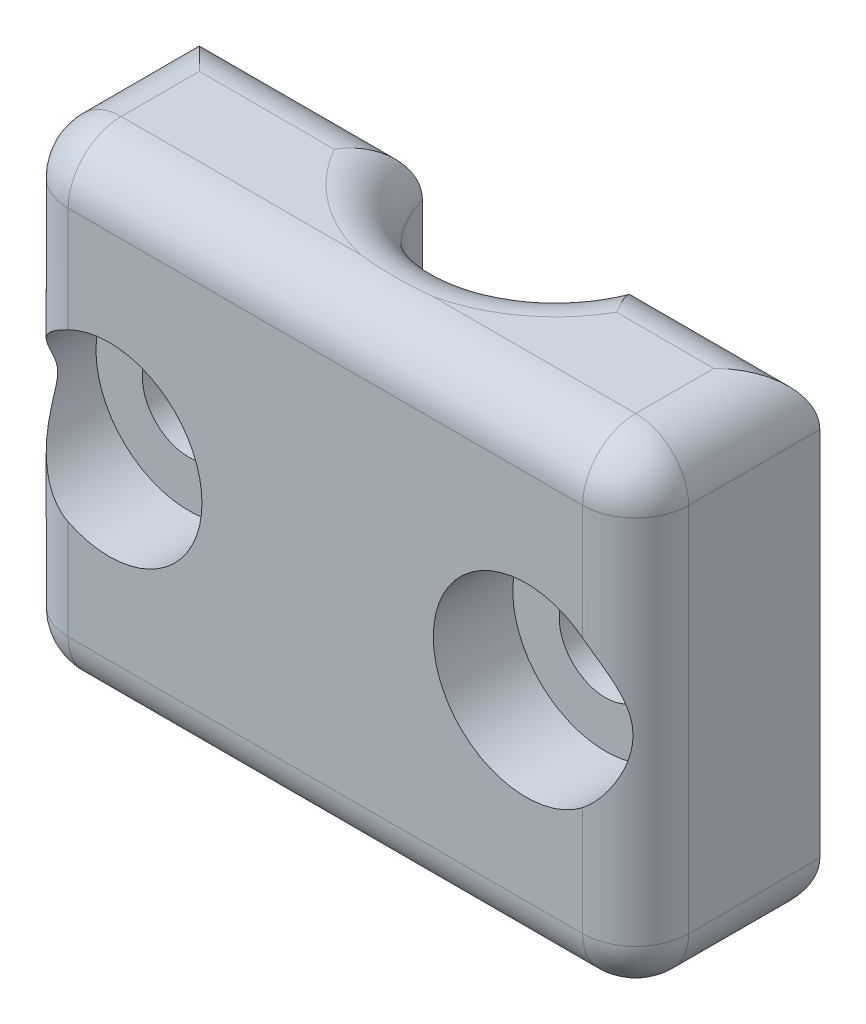
SolidWorks part; units mm, degrees
ref_plane "Front Plane" through (0, 0, 0) normal (0, 0, 1) x (1, 0, 0)
ref_plane "Top Plane" through (0, 0, 0) normal (0, 1, 0) x (1, 0, 0)
ref_plane "Right Plane" through (0, 0, 0) normal (1, 0, 0) x (0, 0, -1)
sketch "Sketch2" plane through (0, -22.2919, 0) normal (0, -1, 0) x (1, 0, 0)
  line L0 (9.0046, 3.0317) -> (0.5858, 3.0317)
  line L1 (24, 3.0317) -> (16.9954, 3.0317)
  line L2 (24, 3.0317) -> (24, 7.9815)
  line L3 (22, 9.9815) -> (2.5858, 9.9815)
  line L4 (0.5858, 3.0317) -> (0.5858, 7.9815)
  arc A1 (16.9954, 3.0317) -> (9.0046, 3.0317) centre (13, 2.0059) ccw
  arc A3 (2.5858, 9.9815) -> (0.5858, 7.9815) centre (2.5858, 7.9815) ccw
  arc A4 (24, 7.9815) -> (22, 9.9815) centre (22, 7.9815) ccw
  point P14 (0.5858, 9.9815)
  dimension "D1" = 2
extrude "Boss-Extrude1" add sketch "Sketch2" against normal blind 18
sketch "Sketch3" plane through (0, 0, 9.9815) normal (0, 0, 1) x (1, 0, 0)
  circle A2 centre (4.1354, -13.3991) radius 1.75
  circle A3 centre (19.8646, -13.3991) radius 1.75
extrude "Cut-Extrude1" cut sketch "Sketch3" against normal blind 18
sketch "Sketch4" plane through (0, 0, 9.9815) normal (0, 0, 1) x (1, 0, 0)
  circle A0 centre (4.1354, -13.3991) radius 3.5
  circle A4 centre (19.8646, -13.3991) radius 3.5
  dimension "D2" = 7
  dimension "D1" = 7
extrude "Cut-Extrude2" cut sketch "Sketch4" against normal blind 3
fillet "Fillet1" radius 2 16 edges at (20.4977, -22.2919, 3.0317) (13, -22.2919, 6.1309) (4.7952, -22.2919, 3.0317) (0.5858, -22.2919, 5.5066) (1.1716, -22.2919, 9.3958) (12.2929, -22.2919, 9.9815) (23.4142, -22.2919, 9.3958) (24, -22.2919, 5.5066) (23.4142, -4.2919, 9.3958) (12.2929, -4.2919, 9.9815) (1.1716, -4.2919, 9.3958) (0.5858, -4.2919, 5.5066) (4.7952, -4.2919, 3.0317) (13, -4.2919, 6.1309) (20.4977, -4.2919, 3.0317) (24, -4.2919, 5.5066)
